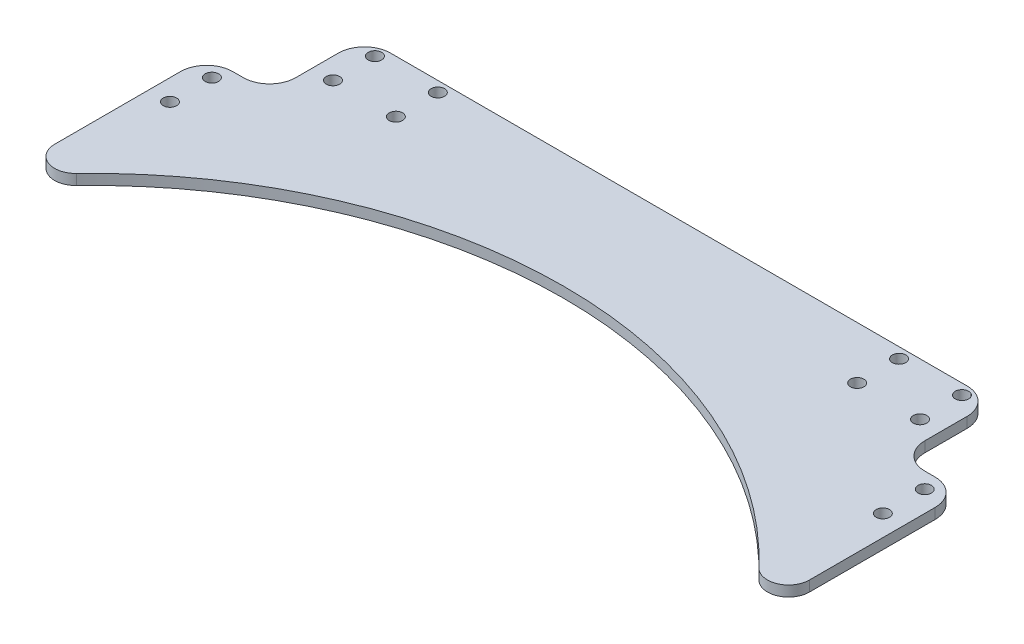
SolidWorks part; units mm, degrees
ref_plane "Front Plane" through (0, 0, 0) normal (0, 0, 1) x (1, 0, 0)
ref_plane "Top Plane" through (0, 0, 0) normal (0, 1, 0) x (1, 0, 0)
ref_plane "Right Plane" through (0, 0, 0) normal (1, 0, 0) x (0, 0, -1)
sketch "Sketch1" plane through (0, 0, 0) normal (0, 1, 0) x (1, 0, 0)
  line L0 (0, 0) -> (0, 92.075)
  line L1 (0, 92.075) -> (228.6, 92.075)
  line L2 (228.6, 92.075) -> (228.6, 0)
  arc A0 (0, 0) -> (228.6, 0) centre (114.3, -85.725) cw
  dimension "D3" = 142.875
  dimension "D1" = 177.8
  dimension "D2" = 228.6
extrude "Boss-Extrude1" add sketch "Sketch1" along normal blind 3.175
sketch "Sketch3" plane through (0, 0, 0) normal (0, -1, 0) x (1, 0, 0)
  line L0 (228.6, -92.075) -> (0, -92.075) construction
  line L1 (114.3, -92.075) -> (114.3, -57.15) construction
  circle A2 centre (44.45, -76.2) radius 2.032 construction
  circle A3 centre (25.4, -76.2) radius 2.032 construction
  arc A8 (0, 0) -> (228.6, 0) centre (114.3, 85.725) ccw construction
  circle A17 centre (44.45, -88.9) radius 2.032 construction
  circle A18 centre (25.4, -88.9) radius 2.032 construction
  circle A19 centre (44.45, -76.2) radius 2.032
  circle A20 centre (25.4, -76.2) radius 2.032
  circle A21 centre (44.45, -88.9) radius 2.032
  circle A22 centre (25.4, -88.9) radius 2.032
  circle A23 centre (203.2, -76.2) radius 2.032
  circle A24 centre (203.2, -88.9) radius 2.032
  circle A25 centre (184.15, -88.9) radius 2.032
  circle A26 centre (184.15, -76.2) radius 2.032
  point P12 (114.3, -92.075)
extrude "Cut-Extrude1" cut sketch "Sketch3" against normal through all
fillet "Fillet1" radius 6.35 2 edges at (0, 1.5875, 0) (228.6, 1.5875, 0)
sketch "Sketch4" plane through (0, 0, 0) normal (0, -1, 0) x (1, 0, 0)
  line L0 (0, -63.3411) -> (19.05, -63.3411)
  line L1 (0, -92.075) -> (0, -17.3036) construction
  line L15 (19.05, -63.3411) -> (19.05, -92.075)
  line L16 (19.05, -92.075) -> (0, -92.075)
  line L17 (0, -92.075) -> (0, -63.3411)
  line L19 (19.05, -70.0557) -> (19.05, 14.5728) construction
  line L21 (209.55, -70.0557) -> (209.55, 14.5728) construction
  line L22 (228.6, -92.075) -> (228.6, -63.3411)
  line L24 (228.6, -63.3411) -> (209.55, -63.3411)
  line L25 (209.55, -63.3411) -> (209.55, -92.075)
  line L26 (228.6, -92.075) -> (0, -92.075) construction
  line L27 (209.55, -92.075) -> (228.6, -92.075)
  circle A0 centre (6.35, -45.8786) radius 2.032
  circle A1 centre (6.35, -58.5786) radius 2.032
  circle A3 centre (222.25, -45.8786) radius 2.032
  circle A4 centre (222.25, -58.5786) radius 2.032
  arc A6 (10.9436, -12.9194) -> (0, -17.3036) centre (6.35, -17.3036) ccw construction
  arc A7 (10.9436, -12.9194) -> (0, -17.3036) centre (6.35, -17.3036) ccw construction
  arc A8 (228.6, -17.3036) -> (217.6564, -12.9194) centre (222.25, -17.3036) ccw construction
  arc A9 (228.6, -17.3036) -> (217.6564, -12.9194) centre (222.25, -17.3036) ccw construction
  line M8 (0, -17.3036) -> (0, -92.075)
  line M9 (0, -92.075) -> (228.6, -92.075)
  line M10 (228.6, -92.075) -> (228.6, -17.3036)
  dimension "D2" = 4.064
  dimension "D1" = 12.7
  dimension "D3" = 28.575
  dimension "D4" = 4.7625
extrude "Cut-Extrude2" cut sketch "Sketch4" against normal through all contours A0 | A1 | A3 | A4 | L15 L0 M8 M9 | L24 L25 M9 M10 region at (219.075, 0, -77.7081) region at (9.525, 0, -77.7081) region at (6.35, 0, -45.8786) region at (6.35, 0, -58.5786) region at (222.25, 0, -45.8786) region at (222.25, 0, -58.5786)
fillet "Fillet2" radius 7.9375 6 edges at (209.55, 1.5875, -92.075) (209.55, 1.5875, -63.3411) (228.6, 1.5875, -63.3411) (19.05, 1.5875, -92.075) (19.05, 1.5875, -63.3411) (0, 1.5875, -63.3411)
